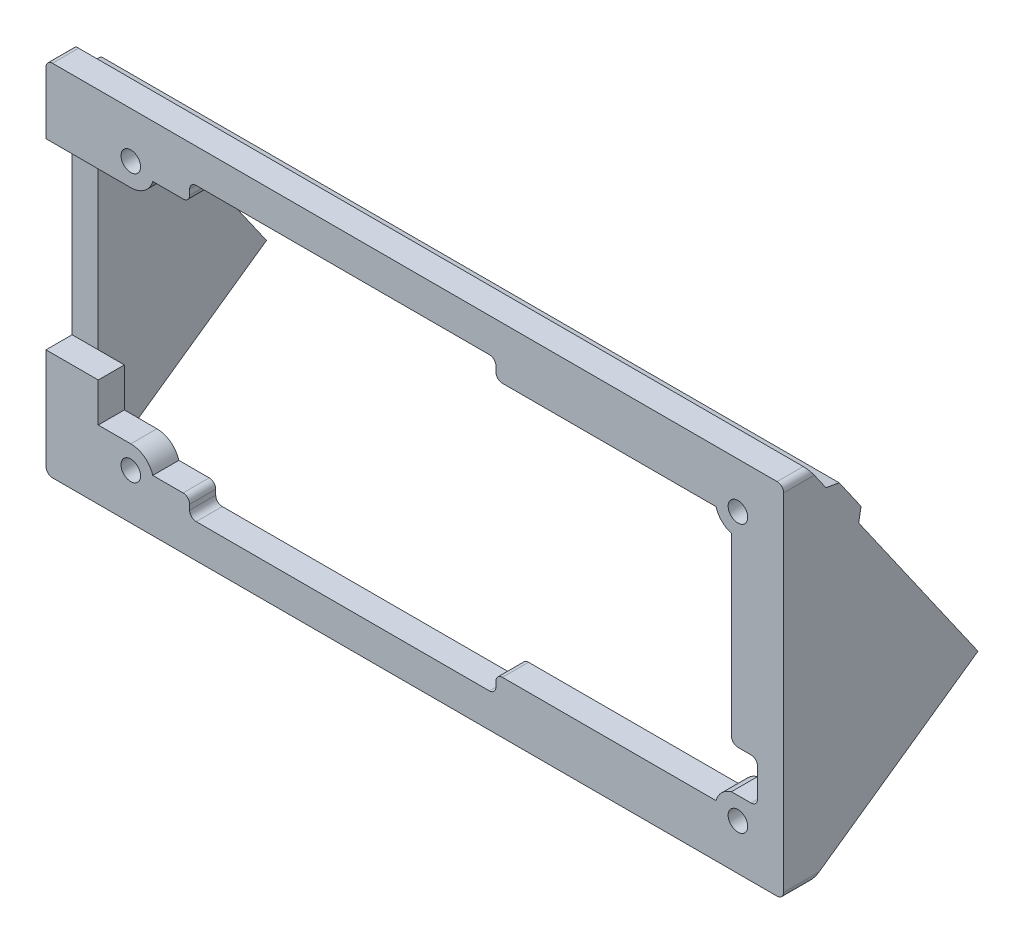
SolidWorks part; units mm, degrees
ref_plane "정면" through (0, 0, 0) normal (0, 0, 1) x (1, 0, 0)
ref_plane "윗면" through (0, 0, 0) normal (0, 1, 0) x (1, 0, 0)
ref_plane "우측면" through (0, 0, 0) normal (1, 0, 0) x (0, 0, -1)
ref_plane "평면1" through (0, 0, 96.6864) normal (0, 0, -1) x (-1, 0, 0)
sketch "스케치1" plane through (0, 0, 96.6864) normal (0, 0, -1) x (-1, 0, 0)
  line L1 (-32.3859, -22.6046) -> (72.6031, -22.6046)
  line L2 (-32.3859, -22.6046) -> (-32.3859, 24.3954)
  line L3 (-32.3859, 24.3954) -> (72.6031, 24.3954)
  line L4 (72.6031, -22.6046) -> (72.6031, 24.3954)
extrude "돌출-얇게1" add sketch "스케치1" along normal blind 4 thin thin type two direction wall 4 second wall 4
sketch "스케치2" plane through (0, 0, 96.6864) normal (0, 0, 1) x (1, 0, 0)
  line L0 (-68.6031, -18.6046) -> (-68.6031, 20.3954) construction
  line L1 (-68.6031, 17.883) -> (-76.6031, 17.883)
  line L2 (-68.6031, 17.883) -> (-68.6031, -10.117)
  line L3 (-68.6031, -10.117) -> (-76.6031, -10.117)
  line L4 (-76.6031, 17.883) -> (-76.6031, -10.117)
  line L5 (-76.6031, -26.6046) -> (-76.6031, 28.3954) construction
  circle A0 centre (-63.6141, -19.6046) radius 1.5
  circle A1 centre (29.3859, -19.6046) radius 1.5
  circle A2 centre (29.3859, 21.3954) radius 1.5
  circle A3 centre (-63.6141, 21.3954) radius 1.5
sketch "스케치3" plane through (0, 0, 92.6864) normal (0, 0, -1) x (-1, 0, 0)
  line L0 (76.6031, -26.6046) -> (76.6031, 28.3954) construction
  line L1 (63.6141, 17.8854) -> (76.6031, 17.8854)
  line L2 (63.6141, 17.8854) -> (63.6141, 24.9054)
  line L3 (63.6141, 24.9054) -> (76.6031, 24.9054)
  line L4 (76.6031, 17.8854) -> (76.6031, 24.9054)
  line L6 (63.6141, -16.0946) -> (76.6031, -16.0946)
  line L7 (63.6141, -16.0946) -> (63.6141, -23.1146)
  line L8 (63.6141, -23.1146) -> (76.6031, -23.1146)
  line L9 (76.6031, -16.0946) -> (76.6031, -23.1146)
  circle A0 centre (63.6141, 21.3954) radius 3.51
  circle A1 centre (63.6141, -19.6046) radius 3.51
  circle A2 centre (-29.3859, -19.6046) radius 3.51
  circle A3 centre (-29.3859, 21.3954) radius 3.51
  line M7 (68.6031, -18.6046) -> (-28.3859, -18.6046)
  line M8 (-28.3859, -18.6046) -> (-28.3859, 20.3954)
  line M9 (-28.3859, 20.3954) -> (68.6031, 20.3954)
  line M10 (68.6031, 20.3954) -> (68.6031, -18.6046)
extrude "보스-돌출1" add sketch "스케치3" against normal up to vertex (4 mm away) contours A3 M8 M9 | A2 M7 M8 | L7 A1 M7 | A1 L7 M7 | A1 L6 M7 M10 | A0 L2 M9 | L2 A0 M9 | A0 L1 M10 M9
extrude "컷-돌출1" cut sketch "스케치2" against normal blind 10
sketch "스케치4" plane through (-76.6031, 0, 0) normal (-1, 0, 0) x (0, 0, 1)
  line L0 (92.6864, 28.3954) -> (66.9137, -8.4932)
  line L3 (92.6864, 28.3954) -> (92.6864, -26.6046)
  line L4 (66.9137, -8.4932) -> (92.6864, -26.6046)
  line L5 (74.6864, 2.6318) -> (74.6864, -13.9553)
  line L6 (74.6864, 2.6318) -> (92.6864, 28.3954)
  line L7 (74.6864, -13.9553) -> (92.6864, -26.6046)
  line M5 (92.6864, 28.3954) -> (92.6864, 17.883)
  dimension "D1" = 45
  dimension "D2" = 31.5
  dimension "D3" = 18
extrude "보스-돌출2" add sketch "스케치4" against normal blind 4 contours L0 L5 L4 L3 M5
ref_plane "평면2" through (-20.1086, 0, 0) normal (-1, 0, 0) x (0, 0, 1)
mirror "대칭 복사1" about plane through (-20.1086, 0, 0) normal (-1, 0, 0) of "보스-돌출2"
sketch "스케치5" plane through (-76.6031, 0, 0) normal (-1, 0, 0) x (0, 0, 1)
  line L0 (85.0754, 17.5017) -> (90.3215, 25.0106)
  line L1 (92.6864, 28.3954) -> (66.9137, -8.4932) construction
  line L2 (84.7159, 19.5277) -> (85.0754, 17.5017) construction
  line L3 (88.2955, 24.6512) -> (90.3215, 25.0106) construction
  line L4 (90.3215, 25.0106) -> (88.2955, 24.6512)
  line L5 (88.2955, 24.6512) -> (84.7159, 19.5277)
  line L6 (84.7159, 19.5277) -> (85.0754, 17.5017)
  line L7 (84.8305, 19.6917) -> (88.1809, 24.4872)
  line L8 (85.1899, 17.6656) -> (90.207, 24.8466)
  line L9 (84.8305, 19.6917) -> (85.1899, 17.6656)
  line L10 (88.1809, 24.4872) -> (90.207, 24.8466)
  line L11 (92.6864, 28.3954) -> (82.3773, 13.6399)
  line L12 (82.3773, 13.6399) -> (84.0168, 12.4945)
  line L20 (84.0168, 12.4945) -> (95.1261, 28.3954)
  line L21 (92.6864, 28.3954) -> (96.6864, 28.3954) construction
  line L22 (95.1261, 28.3954) -> (92.6864, 28.3954)
  point P15 (86.5057, 22.0895)
  point P18 (87.6984, 21.2561)
  line M14 (96.6864, 28.3954) -> (92.6864, 28.3954)
  line M15 (92.6864, 28.3954) -> (66.9137, -8.4932)
  dimension "D1" = 0.2
  dimension "D2" = 0.2
  dimension "D3" = 18
  dimension "D4" = 2
extrude "보스-돌출3" add sketch "스케치5" against normal up to vertex (112.989 mm away) contours L10 L5 L9 L0 | L12 L20 L0 M14 M15
chamfer "모따기1" distance 2 angle 45 1 edges at (-20.1086, 12.4945, 84.0168)
sketch "스케치6" plane through (0, -33.3679, 47.7598) normal (0, 0.5727, -0.8197) x (-1, 0, 0)
  line L0 (-36.3859, 67.6518) -> (76.6031, 67.7433)
  line L1 (-36.3859, 70.5768) -> (-36.3859, 64.7268) construction
  line L2 (-9.8914, 67.6732) -> (50.1086, 67.7219)
  circle A0 centre (-9.8914, 67.6732) radius 2.1
  circle A1 centre (50.1086, 67.7219) radius 2.1
  point P8 (20.1086, 67.6976)
  dimension "D1" = 60
extrude "컷-돌출2" cut sketch "스케치6" against normal blind 4 contours L0 A1 | L0 A1 | L0 A0 | L0 A0
sketch "스케치7" plane through (0, 0, 92.6864) normal (0, 0, -1) x (-1, 0, 0)
  line L0 (-32.3859, -8.4932) -> (-32.3859, -26.6046) construction
  line L1 (-28.3859, -16.2401) -> (-32.3859, -16.2401)
  line L2 (-28.3859, -16.2401) -> (-28.3859, -9.8595)
  line L3 (-28.3859, -9.8595) -> (-32.3859, -9.8595)
  line L4 (-32.3859, -16.2401) -> (-32.3859, -9.8595)
  line L7 (-28.7663, -10.6295) -> (-27.9615, -10.6295) construction
  line L8 (-29.3859, 24.3954) -> (72.6031, 24.3954) construction
  line L9 (54.6041, 24.3954) -> (7.6861, 24.3954)
  line L10 (54.6041, 24.3954) -> (54.6041, -22.6046)
  line L11 (54.6041, -22.6046) -> (7.6861, -22.6046)
  line L12 (7.6861, 24.3954) -> (7.6861, -22.6046)
  line L13 (67.2141, -22.6046) -> (-29.3859, -22.6046) construction
  line L15 (7.6861, 23.1954) -> (54.6041, 23.1954)
  line L16 (7.6861, 23.1954) -> (7.6861, -21.4046)
  line L17 (7.6861, -21.4046) -> (54.6041, -21.4046)
  line L18 (54.6041, 23.1954) -> (54.6041, -21.4046)
  line M6 (-32.3859, 24.9033) -> (-32.3859, -26.6046)
  line M13 (60.2496, -18.6046) -> (-26.0213, -18.6046)
  line M15 (-28.3859, -16.2401) -> (-28.3859, 18.0309)
  line M17 (-26.0213, 20.3954) -> (60.2496, 20.3954)
  dimension "D1" = 0.77
  dimension "D2" = 1.2
  dimension "D3" = 1.2
extrude "컷-돌출3" cut sketch "스케치7" against normal up to vertex (4 mm away) contours L3 L1 M15 M6 | L12 L10 M17 M13 | L15 L12 L10 M17 | L12 L17 L10 M13
fillet "필렛2" radius 1 11 edges at (-7.6861, 20.3954, 94.6864) (-54.6041, 20.3954, 94.6864) (28.3859, -9.8595, 94.6864) (32.3859, -16.2401, 94.6864) (32.3859, -9.8595, 94.6864) (-54.6041, -18.6046, 94.6864) (-7.6861, -18.6046, 94.6864) (-7.6861, -21.4046, 94.6864) (-54.6041, 23.1954, 94.6864) (-54.6041, -21.4046, 94.6864) (-7.6861, 23.1954, 94.6864)
fillet "필렛4" radius 1 4 edges at (36.3859, 28.3954, 94.6864) (-76.6031, 28.3954, 94.6864) (-76.6031, -26.6046, 94.6864) (36.3859, -26.6046, 94.6864)
